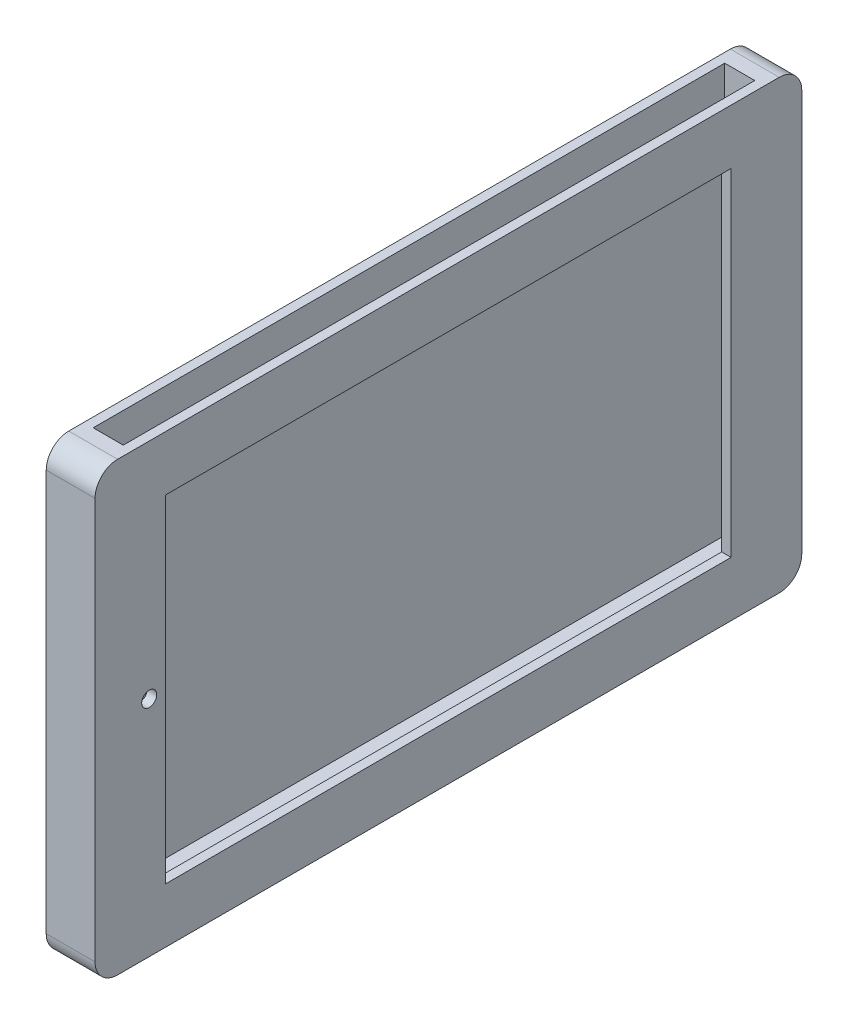
SolidWorks part; units mm, degrees
material "6061-T6 (SS)"
ref_plane "Front Plane" through (0, 0, 0) normal (0, 0, 1) x (1, 0, 0)
ref_plane "Top Plane" through (0, 0, 0) normal (0, 1, 0) x (1, 0, 0)
ref_plane "Right Plane" through (0, 0, 0) normal (1, 0, 0) x (0, 0, -1)
sketch "Sketch1" plane through (0, 0, 0) normal (1, 0, 0) x (0, 0, -1)
  line L1 (-119.38, -75.438) -> (119.38, -75.438)
  line L2 (-119.38, -75.438) -> (-119.38, 75.438)
  line L3 (-119.38, 75.438) -> (119.38, 75.438)
  line L4 (119.38, -75.438) -> (119.38, 75.438)
  line L5 (-119.38, -75.438) -> (119.38, 75.438) construction
  line L6 (-119.38, 75.438) -> (119.38, -75.438) construction
  point P0 (0, 0)
  dimension "D1" = 238.76
  dimension "D2" = 150.876
extrude "Back side" add sketch "Sketch1" along normal blind 3.175
sketch "Sketch2" plane through (3.175, 0, 0) normal (1, 0, 0) x (0, 0, -1)
  line L0 (-119.38, 75.438) -> (-119.38, -75.438) construction
  line L1 (-106.68, -62.738) -> (106.68, -62.738) construction
  line L2 (-106.68, -62.738) -> (-106.68, 62.738) construction
  line L3 (-106.68, 62.738) -> (106.68, 62.738) construction
  line L4 (106.68, -62.738) -> (106.68, 62.738) construction
  line L5 (-106.68, -62.738) -> (106.68, 62.738) construction
  line L6 (-106.68, 62.738) -> (106.68, -62.738) construction
  line L12 (119.38, 75.438) -> (119.38, 9.525)
  line L16 (-106.68, -62.738) -> (106.68, -62.738)
  line L17 (106.68, -62.738) -> (106.68, -9.525)
  line L21 (-106.68, -62.738) -> (-106.68, 75.438)
  line L23 (-119.38, 75.438) -> (-119.38, -75.438)
  line L24 (-119.38, -75.438) -> (119.38, -75.438)
  line L26 (119.38, 75.438) -> (-119.38, 75.438) construction
  line L27 (106.68, 9.525) -> (106.68, 75.438)
  line L28 (-119.38, 75.438) -> (-106.68, 75.438)
  line L29 (106.68, 75.438) -> (119.38, 75.438)
  line L30 (119.38, -75.438) -> (119.38, 75.438) construction
  line L31 (119.38, 9.525) -> (106.68, 9.525)
  line L32 (106.68, -9.525) -> (119.38, -9.525)
  line L33 (119.38, -9.525) -> (119.38, -75.438)
  line L34 (0, 0) -> (119.38, 0) construction
  point P0 (0, 0)
  dimension "D1" = 213.36
  dimension "D2" = 125.476
  dimension "D3" = 12.7
  dimension "D4" = 19.05
extrude "thickeness" add sketch "Sketch2" along normal blind 10.16
sketch "Sketch3" plane through (13.335, 0, 0) normal (1, 0, 0) x (0, 0, -1)
  line L0 (-106.68, -62.738) -> (-106.68, 75.438) construction
  line L1 (-119.38, -75.438) -> (119.38, -75.438)
  line L2 (-119.38, -75.438) -> (-119.38, 75.438)
  line L3 (-119.38, 75.438) -> (119.38, 75.438)
  line L4 (119.38, -75.438) -> (119.38, 75.438)
  line L9 (106.68, -9.525) -> (106.68, -62.738) construction
  line L10 (-95.504, -56.896) -> (95.504, -56.896)
  line L11 (-95.504, -56.896) -> (-95.504, 56.896)
  line L12 (-95.504, 56.896) -> (95.504, 56.896)
  line L13 (95.504, -56.896) -> (95.504, 56.896)
  line L14 (-95.504, -56.896) -> (95.504, 56.896) construction
  line L15 (-95.504, 56.896) -> (95.504, -56.896) construction
  line L16 (106.68, -62.738) -> (-106.68, -62.738) construction
  point P6 (0, 0)
  dimension "D1" = 11.176
  dimension "D2" = 5.842
  dimension "D3" = 11.176
extrude "front side/ screen hole" add sketch "Sketch3" along normal blind 3.175
sketch "Sketch7" plane through (0, 0, 0) normal (-1, 0, 0) x (0, 0, 1)
  line L0 (106.68, 62.738) -> (-106.68, 62.738) construction
  line L1 (85.3186, 43.6626) -> (96.2914, 43.6626)
  line L2 (85.3186, 43.6626) -> (85.3186, 54.6354)
  line L3 (85.3186, 54.6354) -> (96.2914, 54.6354)
  line L4 (96.2914, 43.6626) -> (96.2914, 54.6354)
  line L5 (85.3186, 43.6626) -> (96.2914, 54.6354) construction
  line L6 (85.3186, 54.6354) -> (96.2914, 43.6626) construction
  line L7 (106.68, -62.738) -> (106.68, 75.438) construction
  point P0 (90.805, 49.149)
  dimension "D1" = 10.9728
  dimension "D2" = 13.589
  dimension "D3" = 15.875
extrude "back camera" cut sketch "Sketch7" against normal up to surface (3.175 mm away) up to face at (3.175, 3.175, -56.515)
sketch "Sketch8" plane through (16.51, 0, 0) normal (1, 0, 0) x (0, 0, -1)
  line L0 (-95.504, 0) -> (-106.68, 0) construction
  line L2 (-95.504, 56.896) -> (-95.504, -56.896) construction
  line L3 (-106.68, -62.738) -> (-106.68, 75.438) construction
  circle A0 centre (-101.092, 0) radius 2.54
  dimension "D1" = 5.08
extrude "front camera" cut sketch "Sketch8" against normal up to surface (3.175 mm away) up to face at (13.335, 0, 0)
sketch "Sketch5" plane through (0, 0, 0) normal (0, 0, 1) x (1, 0, 0)
  line L14 (-46.2884, 14.6262) -> (-60.9146, -6.2622) construction
  line L15 (-60.9146, -6.2622) -> (-40.0262, -20.8884) construction
  line L16 (-40.0262, -20.8884) -> (-25.4, 0) construction
  line L17 (-25.4, 0) -> (-46.2884, 14.6262) construction
  line L18 (0, 75.438) -> (0, -75.438) construction
  line L19 (-46.2884, 14.6262) -> (-25.4, 0)
  line L20 (-46.2884, 14.6262) -> (-39.004, 25.0294)
  line L21 (-39.004, 25.0294) -> (-18.1156, 10.4032)
  line L22 (-18.1156, 10.4032) -> (0, 36.275)
  line L23 (0, 36.275) -> (0, -64.4189)
  line L24 (0, -64.4189) -> (-68.199, -16.6654)
  line L25 (-68.199, -16.6654) -> (-60.9146, -6.2622)
  line L26 (-60.9146, -6.2622) -> (-40.0262, -20.8884)
  line L27 (-40.0262, -20.8884) -> (-25.4, 0)
  dimension "D1" = 25.5
  dimension "D2" = 55
  dimension "D3" = 12.7
  dimension "D4" = 25.4
extrude "80-20 attachment" add sketch "Sketch5" along normal mid plane 50.8
fillet "Fillet1" radius 7.62 1 edges at (-18.1156, 10.4032, 0)
fillet "Fillet2" radius 12.7 4 edges at (0, -64.4189, 0) (0, -14.072, 25.4) (0, 36.275, 0) (0, -14.072, -25.4)
fillet "Fillet3" radius 5.08 16 edges at (-1.435, -65.1659, -32.2358) (-8.881, -58.2003, -25.9878) (-1.435, -65.1659, 32.2358) (-8.881, -58.2003, 25.9878) (-0.5878, 36.4603, 34.281) (-6.8358, 26.5124, 26.835) (-13.2225, 17.3913, 25.4) (-31.6807, 19.9017, 25.4) (-0.5878, 36.4603, -34.281) (-31.6807, 19.9017, -25.4) (-18.6637, 13.5116, -25.4) (-13.2225, 17.3913, -25.4) (-40.4495, -36.0958, -25.4) (-40.4495, -36.0958, 25.4) (-18.6637, 13.5116, 25.4) (-6.8358, 26.5124, -26.835)
fillet "Fillet4" radius 7.62 4 edges at (8.255, 75.438, -119.38) (8.255, -75.438, -119.38) (8.255, -75.438, 119.38) (8.255, 75.438, 119.38)
sketch "Sketch6" plane through (-30.267, -43.2257, 0) normal (-0.5736, -0.8192, 0) x (0.8192, -0.5736, 0)
  line L0 (-33.8065, 20.32) -> (-33.8065, -20.32) construction
  line L1 (17.8882, 20.32) -> (-46.3065, 20.32) construction
  line L2 (-46.3065, -20.32) -> (17.8882, -20.32) construction
  line L3 (-46.3065, 20.32) -> (-46.3065, -20.32) construction
  line L4 (0, 0) -> (-46.3065, 0) construction
  circle A0 centre (-33.8065, 13.97) radius 3.3782
  circle A1 centre (-33.8065, -13.97) radius 3.3782
  dimension "D1" = 6.7564
  dimension "D2" = 12.5
  dimension "D3" = 6.35
extrude "Cut-Extrude1" cut sketch "Sketch6" against normal up to surface (50.9 mm away) up to face at (-31.6807, 19.9017, 0)
